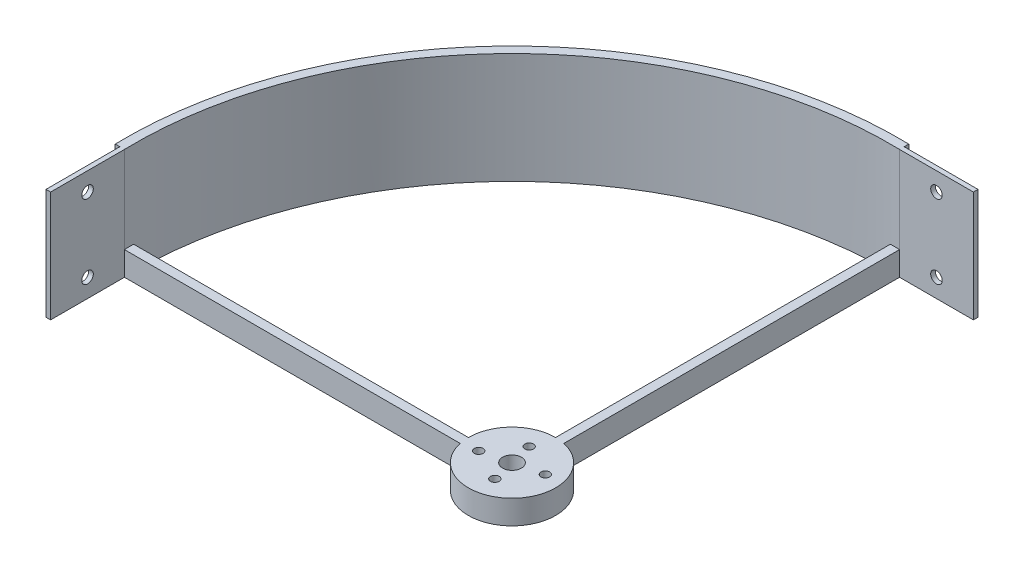
SolidWorks part; units mm, degrees
material "ABS"
ref_plane "Front Plane" through (0, 0, 0) normal (0, 0, 1) x (1, 0, 0)
ref_plane "Top Plane" through (0, 0, 0) normal (0, 1, 0) x (1, 0, 0)
ref_plane "Right Plane" through (0, 0, 0) normal (1, 0, 0) x (0, 0, -1)
sketch "Sketch1" plane through (0, 0, 0) normal (0, 1, 0) x (1, 0, 0)
  line L0 (0, 130.175) -> (0, 9.3426)
  line L1 (3.175, 9.3426) -> (3.175, 130.1363)
  line L2 (0, 0) -> (-22.0351, 22.0351) construction
  line L3 (-22.0351, 22.0351) -> (23.6345, -23.6345) construction
  line L4 (-9.3426, -3.175) -> (-130.1363, -3.175)
  line L5 (-130.175, 0) -> (-9.3426, 0)
  line L6 (3.175, 9.3426) -> (3.175, 130.1363)
  line L7 (3.175, 130.1363) -> (3.175, 133.3122)
  line L8 (-130.1363, -3.175) -> (-133.3122, -3.175)
  circle A0 centre (0, 0) radius 15
  arc A1 (3.175, 130.1363) -> (-130.1363, -3.175) centre (0, 0) ccw
  arc A2 (3.175, 133.3122) -> (-133.3122, -3.175) centre (0, 0) ccw
  dimension "D1" = 30
  dimension "D2" = 133.35
  dimension "D4" = 3.175
  dimension "D3" = 3.175
extrude "Boss-Extrude2" add sketch "Sketch1" along normal blind 8.255 contours A0
extrude "Boss-Extrude3" add sketch "Sketch1<6>" along normal blind 8.255 contours L5 A1 L4 A0 | L6 A1 L0 A0 region at (1.5882, 0, -72.5246) region at (-72.5246, 0, 1.5882)
sketch "Sketch1<6>" plane through (0, 0, 0) normal (0, 1, 0) x (1, 0, 0) same geometry as "Sketch1"
extrude "Boss-Extrude4" add sketch "Sketch1<7>" along normal blind 38.1 contours L7 A2 L8 A1 region at (-93.4129, 0, -93.4129)
sketch "Sketch1<7>" plane through (0, 0, 0) normal (0, 1, 0) x (1, 0, 0) same geometry as "Sketch1"
ref_plane "Plane1" through (-63.4806, 0, -63.4806) normal (0.7071, 0, 0.7071) x (0.7071, 0, -0.7071)
sketch "Sketch5" plane through (0, 8.255, 0) normal (0, 1, 0) x (1, 0, 0)
  line L0 (0, 0) -> (29.635, 0) construction
  line L1 (0, 0) -> (0, 21.5427) construction
  line L2 (0, 130.175) -> (0, 15) construction
  line L3 (0, 0) -> (28.4127, 6.8213) construction
  line L4 (20.7706, 4.9866) -> (-27.0002, -6.4822) construction
  line L5 (0, 0) -> (-5.0645, 21.0953) construction
  line L6 (0, 8) -> (0, 0) construction
  line L7 (0, 0) -> (37.8993, -60.1598) construction
  line L8 (0, 0) -> (-19.6346, 0) construction
  line L9 (-130.175, 0) -> (-15, 0) construction
  circle A0 centre (-9.2375, -2.2177) radius 1.5
  circle A1 centre (-1.8676, 7.779) radius 1.5
  circle A2 centre (1.8676, -7.779) radius 1.5
  circle A3 centre (9.2375, 2.2177) radius 1.5
  circle A6 centre (0, 0) radius 3.25
  point P18 (0, 0)
  dimension "D3" = 3
  dimension "D7" = 3
  dimension "D8" = 6.5
  dimension "D2" = 8
  dimension "D5" = 76.5
  dimension "D6" = 8
  dimension "D9" = 90
  dimension "D10" = 9.5
  dimension "D4" = 57.79
extrude "Cut-Extrude3" cut sketch "Sketch5" against normal blind 63.5
sketch "Sketch6" plane through (0, 0, 3.175) normal (0, 0, 1) x (1, 0, 0)
  line L0 (-14.6601, 0) -> (-133.3122, 0) construction
  line L1 (-130.1363, 38.1) -> (-131.7242, 38.1)
  line L2 (-130.1363, 38.1) -> (-130.1363, 0)
  line L3 (-130.1363, 0) -> (-131.7242, 0)
  line L4 (-131.7242, 38.1) -> (-131.7242, 0)
  line L5 (-130.1363, 38.1) -> (-133.3122, 38.1) construction
  point P7 (-131.7242, 38.1)
extrude "Boss-Extrude5" add sketch "Sketch6" along normal blind 25.4
sketch "Sketch7" plane through (3.175, 0, 0) normal (1, 0, 0) x (0, 0, -1)
  line L0 (14.6601, 0) -> (133.3122, 0) construction
  line L1 (130.1363, 38.1) -> (131.7242, 38.1)
  line L2 (130.1363, 38.1) -> (130.1363, 0)
  line L3 (130.1363, 0) -> (131.7242, 0)
  line L4 (131.7242, 38.1) -> (131.7242, 0)
  line L5 (130.1363, 38.1) -> (133.3122, 38.1) construction
  line L6 (130.1363, 38.1) -> (130.1363, 8.255) construction
  point P7 (131.7242, 38.1)
extrude "Boss-Extrude6" add sketch "Sketch7" along normal blind 25.4
sketch "Sketch8" plane through (-131.7242, 0, 0) normal (-1, 0, 0) x (0, 0, 1)
  line L0 (3.175, 19.05) -> (28.575, 19.05) construction
  line L1 (3.175, 38.1) -> (3.175, 0) construction
  line L2 (28.575, 38.1) -> (28.575, 0) construction
  line L3 (15.875, 19.05) -> (15.875, 31.75) construction
  circle A0 centre (15.875, 31.75) radius 1.9844
  circle A1 centre (15.875, 6.35) radius 1.9844
  dimension "D1" = 3.9688
  dimension "D2" = 12.7
extrude "Cut-Extrude4" cut sketch "Sketch8" against normal up to surface (1.588 mm away) up to face at (-130.1363, 16.891, 13.335)
sketch "Sketch9" plane through (0, 0, -131.7242) normal (0, 0, -1) x (-1, 0, 0)
  line L0 (-28.575, 19.05) -> (-3.175, 19.05) construction
  line L1 (-28.575, 0) -> (-28.575, 38.1) construction
  line L2 (-3.175, 0) -> (-3.175, 38.1) construction
  line L3 (-15.875, 19.05) -> (-15.875, 31.75) construction
  circle A0 centre (-15.875, 31.75) radius 1.9844
  circle A1 centre (-15.875, 6.35) radius 1.9844
  dimension "D1" = 3.9688
  dimension "D2" = 12.7
extrude "Cut-Extrude5" cut sketch "Sketch9" against normal up to next
